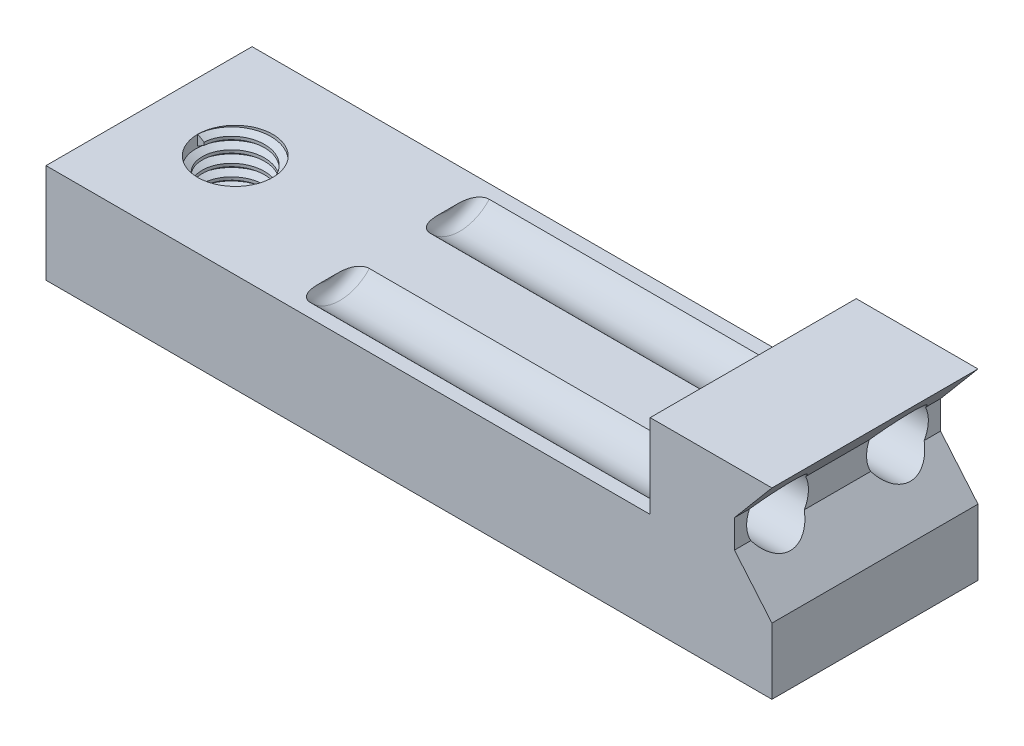
SolidWorks part; units mm, degrees
ref_plane "Front Plane" through (0, 0, 0) normal (0, 0, 1) x (1, 0, 0)
ref_plane "Top Plane" through (0, 0, 0) normal (0, 1, 0) x (1, 0, 0)
ref_plane "Right Plane" through (0, 0, 0) normal (1, 0, 0) x (0, 0, -1)
sketch "Sketch1" plane through (0, 0, 0) normal (0, 1, 0) x (1, 0, 0)
  line L0 (0, 0) -> (77.5005, 0)
  line L1 (77.5005, 0) -> (77.5005, 21.9989)
  line L2 (77.5005, 21.9989) -> (0, 21.9989)
  line L3 (0, 21.9989) -> (0, 0)
  dimension "D1" = 77.5005
  dimension "D2" = 21.9989
extrude "Boss-Extrude1" add sketch "Sketch1" along normal blind 19.5504
sketch "Sketch3" plane through (0, 19.5504, 0) normal (0, 1, 0) x (1, 0, 0)
  line L0 (0, 21.9989) -> (64.5008, 21.9989)
  line L1 (77.5005, 21.9989) -> (0, 21.9989) construction
  line L2 (64.5008, 21.9989) -> (64.5008, 0)
  line L3 (0, 0) -> (77.5005, 0) construction
  line L4 (64.5008, 0) -> (0, 0)
  line L5 (0, 0) -> (0, 21.9989)
  dimension "D1" = 64.5008
extrude "Cut-Extrude1" cut sketch "Sketch3" against normal blind 8.951
sketch "Sketch4" plane through (77.5005, 0, 0) normal (1, 0, 0) x (0, 0, -1)
  line L0 (0, 19.5504) -> (21.9989, 19.5504) construction
  line L1 (21.9989, 19.5504) -> (21.9989, 0) construction
  line L2 (0, 19.5504) -> (0, 0) construction
  circle A0 centre (4.5999, 13.4544) radius 3.2969
  circle A1 centre (17.399, 13.4544) radius 3.2969
  dimension "D5" = 6.5938
  dimension "D6" = 6.5938
  dimension "D1" = 6.096
  dimension "D2" = 6.096
  dimension "D3" = 4.5999
  dimension "D4" = 4.5999
extrude "Cut-Extrude2" cut sketch "Sketch4" against normal blind 38.1
sketch "Sketch5" plane through (64.5008, 0, 0) normal (-1, 0, 0) x (0, 0, 1)
  circle A0 centre (-17.399, 13.4544) radius 4.2494
  circle A1 centre (-4.5999, 13.4544) radius 4.2494
  dimension "D1" = 8.4988
  dimension "D2" = 8.4988
extrude "Cut-Extrude3" cut sketch "Sketch5" against normal blind 2.9997 and the other way blind 38.9992
fillet "Fillet3" radius 1.27 2 edges at (25.5016, 9.205, -4.5999) (25.5016, 9.205, -17.399)
sketch "Sketch6" plane through (0, 0, 0) normal (0, 0, 1) x (1, 0, 0)
  line L0 (77.5005, 7.051) -> (73.5, 11.8008)
  line L1 (77.5005, 19.5504) -> (77.5005, 0) construction
  line L2 (73.5, 11.8008) -> (73.5, 14.8006)
  line L3 (73.5, 14.8006) -> (77.5005, 19.5504)
  line L4 (77.5005, 19.5504) -> (77.5005, 7.051)
  dimension "D1" = 7.051
  dimension "D2" = 4.0005
  dimension "D3" = 4.7498
  dimension "D4" = 2.9997
extrude "Cut-Extrude4" cut sketch "Sketch6" against normal through all
sketch "Sketch7" plane through (0, 10.5994, 0) normal (0, 1, 0) x (1, 0, 0)
  line L0 (0, 21.9989) -> (0, 0) construction
  line L1 (0, 0) -> (64.5008, 0) construction
  circle A0 centre (9.1999, 11.0007) radius 4
  dimension "D3" = 8
  dimension "D1" = 9.1999
  dimension "D2" = 11.0007
extrude "Cut-Extrude5" cut sketch "Sketch7" against normal through all
thread "Thread1" pitch 1.25 method extrude profile "Thread Profile1" start angle 0, offset 0, length 9.4996, pitch 1.25, diameter 8
ref_plane "Plane1" through (5.1999, 10.5994, -11.0007) normal (0, 0, 1) x (-1, 0, 0)
sketch "Thread Profile1" plane through (5.1999, 10.5994, -11.0007) normal (0, 0, 1) x (-1, 0, 0)
  line L0 (0, 0) -> (0, 1.25) construction
  line L11 (0, 0) -> (0, 1.0937)
  line L12 (0, 1.0937) -> (-0.6766, 0.7031)
  line L13 (-0.6766, 0.7031) -> (-0.6766, 0.3906)
  line L15 (-0.6766, 0.3906) -> (0, 0)
  line L17 (-0.6766, 0.5469) -> (0, 0.5469) construction
  point P2 (0, 0)
  dimension "Pitch" = 1.25
  dimension "Profile_Angle" = 60
  dimension "Profile_Land" = 0.3125
  dimension "Profile_Height" = 0.6766
